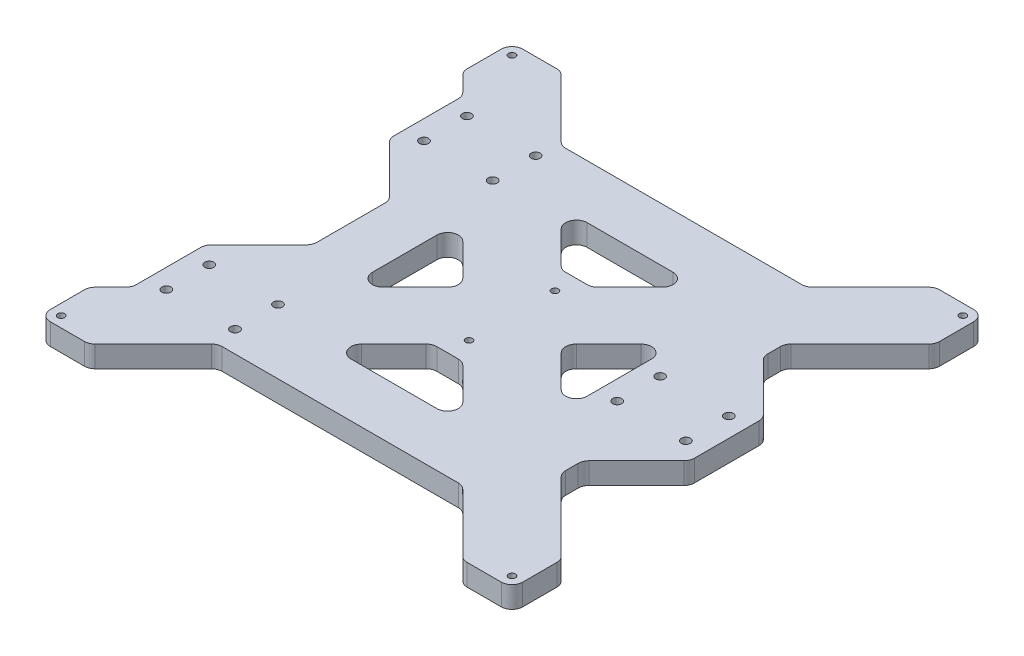
SolidWorks part; units mm, degrees
material "Стекло"
ref_plane "Спереди" through (0, 0, 0) normal (0, 0, 1) x (1, 0, 0)
ref_plane "Сверху" through (0, 0, 0) normal (0, 1, 0) x (1, 0, 0)
ref_plane "Справа" through (0, 0, 0) normal (1, 0, 0) x (0, 0, -1)
sketch "Эскиз1" plane through (0, 0, 0) normal (0, 1, 0) x (1, 0, 0)
  line L0 (-91.6084, 0) -> (86.7133, 0) construction
  line L1 (0, 12.0467) -> (0, -12.5306) construction
  line L2 (-275.537, 125) -> (163.8032, 125) construction
  line L3 (-105, 105) -> (105, 105) construction
  line L4 (-105, 105) -> (-105, -105) construction
  line L5 (-105, -105) -> (105, -105) construction
  line L6 (105, 105) -> (105, -105) construction
  line L7 (-105, 105) -> (105, -105) construction
  line L8 (-105, -105) -> (105, 105) construction
  line L9 (-105, 110) -> (-89.1421, 110)
  line L10 (-55, 125) -> (55, 125) construction
  line L11 (-55, 125) -> (-55, 80) construction
  line L12 (-55, 80) -> (55, 80)
  line L13 (55, 125) -> (55, 80) construction
  line L14 (58.5355, 81.4645) -> (85.6066, 108.5355)
  line L15 (105, 110) -> (89.1421, 110)
  line L16 (-110, 105) -> (-110, 89.1421)
  line L17 (-75, 244.1659) -> (-75, -244.1659) construction
  line L18 (75, 229.144) -> (75, -229.144) construction
  line L19 (-85.6066, 108.5355) -> (-58.5355, 81.4645)
  line L20 (-55, 75) -> (-95, 75) construction
  line L21 (-55, 75) -> (-55, 45) construction
  line L22 (-55, 45) -> (-95, 45) construction
  line L23 (-95, 75) -> (-95, 45) construction
  line L24 (-55, 75) -> (-95, 45) construction
  line L25 (-55, 45) -> (-95, 75) construction
  line L26 (-55, -45) -> (-95, -45) construction
  line L27 (-55, -45) -> (-55, -75) construction
  line L28 (-55, -75) -> (-95, -75) construction
  line L29 (-95, -45) -> (-95, -75) construction
  line L30 (-55, -45) -> (-95, -75) construction
  line L31 (-55, -75) -> (-95, -45) construction
  line L32 (-101.4645, 78.5355) -> (-108.5355, 85.6066)
  line L33 (-100, 45) -> (-100, 75)
  line L34 (-98.5355, 41.4645) -> (-76.4645, 19.3934)
  line L35 (-110, -105) -> (-110, -89.1421)
  line L36 (-76.4645, -19.3934) -> (-98.5355, -41.4645)
  line L37 (-100, -45) -> (-100, -75)
  line L38 (-101.4645, -78.5355) -> (-108.5355, -85.6066)
  line L39 (-75, 15.8579) -> (-75, -15.8579)
  line L40 (110, 105) -> (110, 89.1421)
  line L41 (95, -15) -> (55, -15) construction
  line L42 (95, -15) -> (95, 15) construction
  line L43 (95, 15) -> (55, 15) construction
  line L44 (55, -15) -> (55, 15) construction
  line L45 (95, -15) -> (55, 15) construction
  line L46 (95, 15) -> (55, -15) construction
  line L47 (108.5355, 85.6066) -> (76.4645, 53.5355)
  line L48 (75, 50) -> (75, 44.1421)
  line L49 (98.5355, 18.5355) -> (76.4645, 40.6066)
  line L50 (100, 15) -> (100, -15)
  line L51 (110, -105) -> (110, -89.1421)
  line L52 (108.5355, -85.6066) -> (76.4645, -53.5355)
  line L53 (98.5355, -18.5355) -> (76.4645, -40.6066)
  line L54 (75, -44.1421) -> (75, -50)
  line L55 (-105, -110) -> (-89.1421, -110)
  line L56 (105, -110) -> (89.1421, -110)
  line L57 (-58.5355, -81.4645) -> (-85.6066, -108.5355)
  line L58 (58.5355, -81.4645) -> (85.6066, -108.5355)
  line L59 (-159.2512, -80) -> (161.4197, -80) construction
  line L60 (-55, -80) -> (55, -80)
  line L61 (-23.5355, -46.4645) -> (-8.5355, -31.4645)
  line L62 (-91, 70) -> (-59, 70) construction
  line L63 (-91, 70) -> (-91, 50) construction
  line L64 (-91, 50) -> (-59, 50) construction
  line L65 (-59, 70) -> (-59, 50) construction
  line L66 (-91, 70) -> (-59, 50) construction
  line L67 (-91, 50) -> (-59, 70) construction
  line L68 (-91, -70) -> (-59, -70) construction
  line L69 (-91, -70) -> (-91, -50) construction
  line L70 (-91, -50) -> (-59, -50) construction
  line L71 (-59, -70) -> (-59, -50) construction
  line L72 (-91, -70) -> (-59, -50) construction
  line L73 (-91, -50) -> (-59, -70) construction
  line L74 (59, 10) -> (91, 10) construction
  line L75 (59, 10) -> (59, -10) construction
  line L76 (59, -10) -> (91, -10) construction
  line L77 (91, 10) -> (91, -10) construction
  line L78 (59, 10) -> (91, -10) construction
  line L79 (59, -10) -> (91, 10) construction
  line L80 (-13.5, 25) -> (13.5, 25) construction
  line L81 (-13.5, 25) -> (-13.5, -25) construction
  line L82 (-13.5, -25) -> (13.5, -25) construction
  line L83 (13.5, 25) -> (13.5, -25) construction
  line L84 (-13.5, 25) -> (13.5, -25) construction
  line L85 (-13.5, -25) -> (13.5, 25) construction
  line L86 (23.5355, 46.4645) -> (8.5355, 31.4645)
  line L87 (23.5355, -46.4645) -> (8.5355, -31.4645)
  line L88 (-5, 30) -> (5, 30)
  line L89 (-20, 55) -> (20, 55)
  line L90 (-23.5355, 46.4645) -> (-8.5355, 31.4645)
  line L91 (-20, -55) -> (20, -55)
  line L92 (-5, -30) -> (5, -30)
  line L93 (-50, 15) -> (-50, -15)
  line L94 (-41.4645, 18.5355) -> (-26.4645, 3.5355)
  line L95 (-41.4645, -18.5355) -> (-26.4645, -3.5355)
  line L96 (-18.5, -10) -> (-18.5, 15)
  line L97 (41.4645, 18.5355) -> (26.4645, 3.5355)
  line L98 (41.4645, -18.5355) -> (26.4645, -3.5355)
  line L99 (50, 15) -> (50, -15)
  arc A0 (-105, 110) -> (-110, 105) centre (-105, 105) ccw
  arc A1 (110, 105) -> (105, 110) centre (105, 105) ccw
  circle A2 centre (105, 105) radius 1.6
  arc A3 (-110, -105) -> (-105, -110) centre (-105, -105) ccw
  arc A4 (-58.5355, 81.4645) -> (-55, 80) centre (-55, 85) ccw
  arc A5 (-85.6066, 108.5355) -> (-89.1421, 110) centre (-89.1421, 105) ccw
  arc A6 (55, 80) -> (58.5355, 81.4645) centre (55, 85) ccw
  arc A7 (89.1421, 110) -> (85.6066, 108.5355) centre (89.1421, 105) ccw
  arc A8 (-110, 89.1421) -> (-108.5355, 85.6066) centre (-105, 89.1421) ccw
  arc A9 (-108.5355, -85.6066) -> (-110, -89.1421) centre (-105, -89.1421) ccw
  arc A10 (-100, 75) -> (-101.4645, 78.5355) centre (-105, 75) ccw
  arc A11 (-75, 15.8579) -> (-76.4645, 19.3934) centre (-80, 15.8579) ccw
  arc A12 (-100, 45) -> (-98.5355, 41.4645) centre (-95, 45) ccw
  arc A13 (-98.5355, -41.4645) -> (-100, -45) centre (-95, -45) ccw
  arc A14 (-101.4645, -78.5355) -> (-100, -75) centre (-105, -75) ccw
  arc A15 (-76.4645, -19.3934) -> (-75, -15.8579) centre (-80, -15.8579) ccw
  arc A16 (108.5355, 85.6066) -> (110, 89.1421) centre (105, 89.1421) ccw
  arc A17 (76.4645, 53.5355) -> (75, 50) centre (80, 50) ccw
  arc A18 (100, 15) -> (98.5355, 18.5355) centre (95, 15) ccw
  arc A19 (75, 44.1421) -> (76.4645, 40.6066) centre (80, 44.1421) ccw
  arc A20 (98.5355, -18.5355) -> (100, -15) centre (95, -15) ccw
  arc A21 (76.4645, -40.6066) -> (75, -44.1421) centre (80, -44.1421) ccw
  arc A22 (110, -89.1421) -> (108.5355, -85.6066) centre (105, -89.1421) ccw
  arc A23 (75, -50) -> (76.4645, -53.5355) centre (80, -50) ccw
  arc A24 (-89.1421, -110) -> (-85.6066, -108.5355) centre (-89.1421, -105) ccw
  arc A25 (85.6066, -108.5355) -> (89.1421, -110) centre (89.1421, -105) ccw
  arc A26 (58.5355, -81.4645) -> (55, -80) centre (55, -85) ccw
  arc A27 (-55, -80) -> (-58.5355, -81.4645) centre (-55, -85) ccw
  arc A28 (105, -110) -> (110, -105) centre (105, -105) ccw
  circle A29 centre (105, -105) radius 1.6
  circle A30 centre (-105, -105) radius 1.6
  circle A31 centre (-105, 105) radius 1.6
  circle A32 centre (-91, 70) radius 2.1
  circle A33 centre (-59, 70) radius 2.1
  circle A34 centre (-59, 50) radius 2.1
  circle A35 centre (-91, 50) radius 2.1
  circle A36 centre (-59, -50) radius 2.1
  circle A37 centre (-91, -50) radius 2.1
  circle A38 centre (-91, -70) radius 2.1
  circle A39 centre (-59, -70) radius 2.1
  circle A40 centre (91, -10) radius 2.1
  circle A41 centre (59, -10) radius 2.1
  circle A42 centre (59, 10) radius 2.1
  circle A43 centre (91, 10) radius 2.1
  circle A44 centre (0, -20) radius 1.6
  circle A45 centre (0, 20) radius 1.6
  arc A46 (-20, 55) -> (-23.5355, 46.4645) centre (-20, 50) ccw
  arc A47 (23.5355, 46.4645) -> (20, 55) centre (20, 50) ccw
  arc A48 (-8.5355, 31.4645) -> (-5, 30) centre (-5, 35) ccw
  arc A49 (5, 30) -> (8.5355, 31.4645) centre (5, 35) ccw
  arc A50 (-23.5355, -46.4645) -> (-20, -55) centre (-20, -50) ccw
  arc A51 (20, -55) -> (23.5355, -46.4645) centre (20, -50) ccw
  arc A52 (-5, -30) -> (-8.5355, -31.4645) centre (-5, -35) ccw
  arc A53 (8.5355, -31.4645) -> (5, -30) centre (5, -35) ccw
  arc A54 (-41.4645, 18.5355) -> (-50, 15) centre (-45, 15) ccw
  arc A55 (-50, -15) -> (-41.4645, -18.5355) centre (-45, -15) ccw
  arc A56 (-26.4645, -3.5355) -> (-26.4645, 3.5355) centre (-30, 0) ccw
  arc A57 (26.4645, 3.5355) -> (26.4645, -3.5355) centre (30, 0) ccw
  arc A58 (50, 15) -> (41.4645, 18.5355) centre (45, 15) ccw
  arc A59 (41.4645, -18.5355) -> (50, -15) centre (45, -15) ccw
  point P4 (0, 0)
  point P20 (0, 125)
  point P37 (-75, 0)
  point P38 (75, 0)
  point P39 (-75, 60)
  point P44 (-75, -60)
  point P61 (75, 0)
  point P115 (-75, 60)
  point P123 (-75, -60)
  point P128 (75, 0)
  point P145 (0, 0)
  dimension "D3" = 10
  dimension "D7" = 5
  dimension "D15" = 3.2
  dimension "D18" = 4.2
  dimension "D1" = 210
  dimension "D2" = 210
  dimension "D4" = 125
  dimension "D5" = 45
  dimension "D6" = 110
  dimension "D8" = 75
  dimension "D9" = 75
  dimension "D10" = 30
  dimension "D11" = 40
  dimension "D12" = 60
  dimension "D13" = 60
  dimension "D14" = 30
  dimension "D16" = 32
  dimension "D17" = 20
  dimension "D19" = 50
  dimension "D20" = 27
  dimension "D21" = 20
  dimension "D22" = 20
  dimension "D24" = 5
  dimension "D23" = 25
  dimension "D25" = 5
  dimension "D26" = 25
  dimension "D27" = 25
  dimension "D28" = 5
  dimension "D29" = 5
extrude "Бобышка-Вытянуть1" add sketch "Эскиз1" along normal blind 10 contours A23 L54 A21 L53 A20 L50 A18 L49 A19 L48 A17 L47 A16 L40 A1 L15 A7 L14 A6 L12 A4 L19 A5 L9 A0 L16 A8 L32 A10 L33 A12 L34 A11 L39 A15 L36 A13 L37 A14 L38 A9 L35 A3 L51 A22 L52 | A3 region at (-0.6199, 0, 0)
equation "\"D4@Эскиз1\"=450/2-200/2"
equation "\"D8@Эскиз1\"=150/2"
equation "\"D9@Эскиз1\"=150/2"
